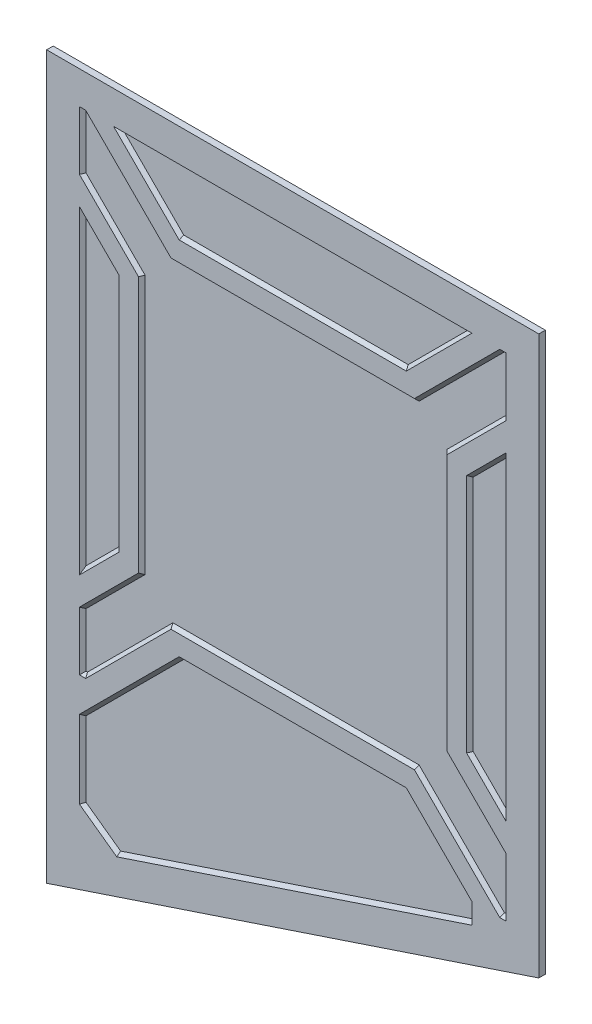
SolidWorks part; units mm, degrees
ref_plane "Plan de face" through (0, 0, 0) normal (0, 0, 1) x (1, 0, 0)
ref_plane "Plan de dessus" through (0, 0, 0) normal (0, 1, 0) x (1, 0, 0)
ref_plane "Plan de droite" through (0, 0, 0) normal (1, 0, 0) x (0, 0, -1)
sketch "Esquisse1" plane through (0, 0, 0) normal (0, 0, 1) x (1, 0, 0)
  line L0 (750, 0) -> (0, -250)
  line L1 (0, 0) -> (750, 0) construction
  line L2 (0, 0) -> (0, 850)
  line L3 (0, 850) -> (750, 850)
  line L4 (750, 0) -> (750, 850)
  line L5 (0, -250) -> (0, 0)
  dimension "D1" = 850
  dimension "D2" = 750
  dimension "D3" = 1100
extrude "Boss.-Extru.1" add sketch "Esquisse1" along normal blind 10
sketch "Esquisse2" plane through (0, 0, 10) normal (0, 0, 1) x (1, 0, 0)
  line L0 (189.4975, 670) -> (140, 620.5025) construction
  line L1 (110, 241.9239) -> (110, 608.0761)
  line L2 (110, 608.0761) -> (50, 668.0761)
  line L3 (201.9239, 700) -> (548.0761, 700)
  line L4 (375, 850) -> (375, -125) construction
  line L5 (750, 850) -> (0, 850) construction
  line L6 (50, 800) -> (50, 710.5025)
  line L7 (50, 710.5025) -> (140, 620.5025)
  line L8 (0, -250) -> (750, 0) construction
  line L9 (750, 425) -> (0, 425) construction
  line L10 (750, 0) -> (750, 850) construction
  line L11 (0, 850) -> (0, -250) construction
  line L12 (50, 800) -> (50, 50) construction
  line L13 (610, 670) -> (560.5025, 670) construction
  line L14 (610, 620.5025) -> (610, 670) construction
  line L15 (700, 800) -> (50, 800) construction
  line L16 (140, 620.5025) -> (140, 229.4975)
  line L17 (50, 800) -> (59.4975, 800)
  line L18 (59.4975, 800) -> (189.4975, 670)
  line L19 (560.5025, 670) -> (189.4975, 670)
  line L20 (648.0761, 800) -> (101.9239, 800)
  line L21 (101.9239, 800) -> (201.9239, 700)
  line L22 (700, 800) -> (700, 50) construction
  line L23 (50, 668.0761) -> (50, 181.9239)
  line L24 (560.5025, 670) -> (610, 620.5025) construction
  line L25 (140, 620.5025) -> (140, 670) construction
  line L26 (140, 670) -> (189.4975, 670) construction
  line L27 (700, 668.0761) -> (700, 181.9239)
  line L28 (648.0761, 800) -> (548.0761, 700)
  line L29 (690.5025, 800) -> (560.5025, 670)
  line L30 (700, 800) -> (690.5025, 800)
  line L31 (610, 620.5025) -> (610, 229.4975)
  line L32 (700, 710.5025) -> (610, 620.5025)
  line L33 (700, 800) -> (700, 710.5025)
  line L34 (640, 608.0761) -> (700, 668.0761)
  line L35 (640, 241.9239) -> (640, 608.0761)
  line L36 (140, 180) -> (189.4975, 180) construction
  line L37 (140, 229.4975) -> (140, 180) construction
  line L38 (560.5025, 180) -> (610, 229.4975) construction
  line L39 (700, 50) -> (50, 50) construction
  line L40 (610, 229.4975) -> (610, 180) construction
  line L41 (610, 180) -> (560.5025, 180) construction
  line L42 (189.4975, 180) -> (140, 229.4975) construction
  line L43 (640, 241.9239) -> (700, 181.9239)
  line L44 (700, 50) -> (700, 139.4975)
  line L45 (700, 139.4975) -> (610, 229.4975)
  line L46 (700, 50) -> (690.5025, 50)
  line L47 (690.5025, 50) -> (560.5025, 180)
  line L48 (648.0761, 50) -> (548.0761, 150)
  line L49 (101.9239, 50) -> (201.9239, 150)
  line L50 (648.0761, 50) -> (101.9239, 50) construction
  line L51 (560.5025, 180) -> (189.4975, 180)
  line L52 (59.4975, 50) -> (189.4975, 180)
  line L53 (50, 50) -> (59.4975, 50)
  line L54 (50, 139.4975) -> (140, 229.4975)
  line L55 (50, 50) -> (50, 139.4975)
  line L56 (201.9239, 150) -> (548.0761, 150)
  line L57 (110, 241.9239) -> (50, 181.9239)
  line L58 (101.9239, 50) -> (50, -1.9239)
  line L59 (50, -1.9239) -> (50, -120.6287)
  line L60 (106.921, -161.655) -> (648.0761, 18.73)
  line L61 (648.0761, 18.73) -> (648.0761, 50)
  line L62 (50, -120.6287) -> (106.921, -161.655)
  point P5 (375, 180)
  point P20 (375, 670)
  point P23 (590, 425)
  point P29 (375, 670)
  point P31 (375, 700)
  point P32 (375, 800)
  point P33 (110, 425)
  point P34 (140, 425)
  point P37 (375, 700)
  point P39 (610, 425)
  point P40 (375, 700)
  point P41 (375, 670)
  point P47 (620, 425)
  point P59 (640, 425)
  point P61 (610, 425)
  point P64 (700, 425)
  point P65 (50, 425)
  point P68 (140, 425)
  point P70 (110, 425)
  point P71 (375, 150)
  point P72 (610, 425)
  point P73 (140, 425)
  point P74 (375, 50)
  point P77 (50, -180.6287)
  dimension "D2" = 90
  dimension "D3" = 130
  dimension "D4" = 70
  dimension "D5" = 45
  dimension "D6" = 30
  dimension "D7" = 30
  dimension "D8" = 30
  dimension "D9" = 30
  dimension "D1" = 50
  dimension "D10" = 50
  dimension "D11" = 50
  dimension "D12" = 50
extrude "Enlèv. mat.-Extru.1" cut sketch "Esquisse2" against normal blind 5
chamfer "Chanfrein1" distance 5 angle 45 39 edges at (50, 425, 5) (80, 638.0761, 5) (124.4975, 735, 5) (375, 670, 5) (140, 425, 5) (95, 665.5025, 5) (50, 755.2513, 5) (54.7487, 800, 5) (375, 800, 5) (375, 700, 5) (151.9239, 750, 5) (110, 425, 5) (80, 211.9239, 5) (625.5025, 735, 5) (695.2513, 800, 5) (700, 755.2513, 5) (655, 665.5025, 5) (610, 425, 5) (655, 184.4975, 5) (700, 94.7487, 5) (695.2513, 50, 5) (625.5025, 115, 5) (375, 180, 5) (124.4975, 115, 5) (54.7487, 50, 5) (50, 94.7487, 5) (95, 184.4975, 5) (598.0761, 750, 5) (700, 425, 5) (670, 211.9239, 5) (640, 425, 5) (670, 638.0761, 5) (375, 150, 5) (598.0761, 100, 5) (648.0761, 34.365, 5) (377.4986, -71.4625, 5) (78.4605, -141.1419, 5) (50, -61.2763, 5) (125.9619, 74.0381, 5)
